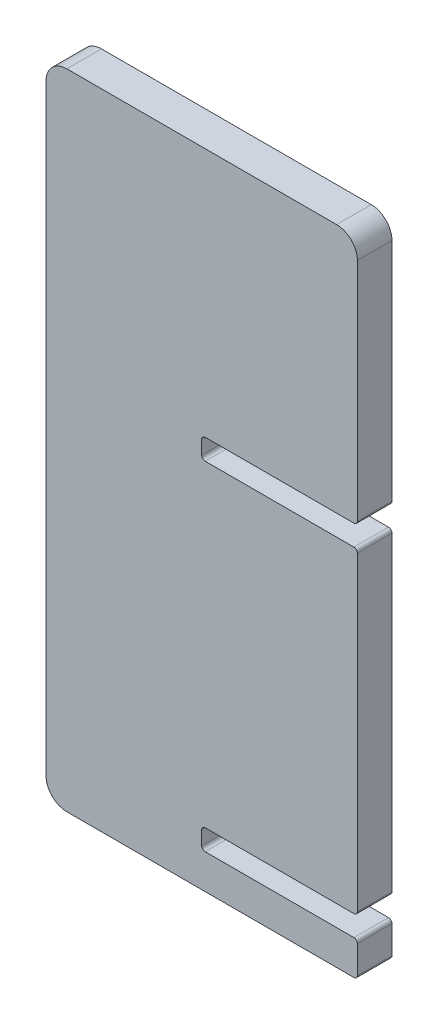
SolidWorks part; units mm, degrees
ref_plane "Alzado" through (0, 0, 0) normal (0, 0, 1) x (1, 0, 0)
ref_plane "Planta" through (0, 0, 0) normal (0, 1, 0) x (1, 0, 0)
ref_plane "Vista lateral" through (0, 0, 0) normal (1, 0, 0) x (0, 0, -1)
sketch "Croquis1" plane through (0, 0, 0) normal (0, 0, 1) x (1, 0, 0)
  line L1 (-22.5, 45) -> (22.5, 45)
  line L2 (-22.5, 45) -> (-22.5, -48)
  line L3 (-22.5, -48) -> (22.5, -48)
  line L4 (22.5, 45) -> (22.5, -48)
  dimension "D1" = 45
  dimension "D2" = 22.5
  dimension "D3" = 93
  dimension "D4" = 45
extrude "Saliente-Extruir1" add sketch "Croquis1" along normal blind 5 contours L2 L3 L4 L1
sketch "Croquis2" plane through (0, 0, 5) normal (0, 0, 1) x (1, 0, 0)
  line L0 (22.5, 45) -> (22.5, -48) construction
  line L1 (22.5, 8.8795) -> (0, 8.8795)
  line L2 (22.5, 8.8795) -> (22.5, 5.8795)
  line L3 (22.5, 5.8795) -> (0, 5.8795)
  line L4 (0, 8.8795) -> (0, 5.8795)
  dimension "D1" = 22.5
  dimension "D2" = 3
  dimension "D3" = 5.8795
extrude "Cortar-Extruir1" cut sketch "Croquis2" against normal up to surface (5 mm away) up to face at (0, -1.5, 0)
sketch "Croquis3" plane through (0, 0, 5) normal (0, 0, 1) x (1, 0, 0)
  line L0 (22.5, 5.8795) -> (22.5, -48) construction
  line L1 (22.5, -40) -> (0, -40)
  line L2 (22.5, -40) -> (22.5, -43)
  line L3 (22.5, -43) -> (0, -43)
  line L4 (0, -40) -> (0, -43)
  line L5 (-22.5, -48) -> (22.5, -48) construction
  dimension "D1" = 3
  dimension "D2" = 5
  dimension "D3" = 22.5
extrude "Cortar-Extruir2" cut sketch "Croquis3" against normal up to surface (5 mm away) up to face at (5.625, 2.9397, 0)
fillet "Redondeo1" radius 3 3 edges at (-22.5, -48, 2.5) (22.5, 45, 2.5) (-22.5, 45, 2.5)
fillet "Redondeo2" radius 0.5 9 edges at (22.5, 5.8795, 2.5) (22.5, 8.8795, 2.5) (0, 8.8795, 2.5) (0, 5.8795, 2.5) (22.5, -43, 2.5) (0, -43, 2.5) (0, -40, 2.5) (22.5, -40, 2.5) (22.5, -48, 2.5)
